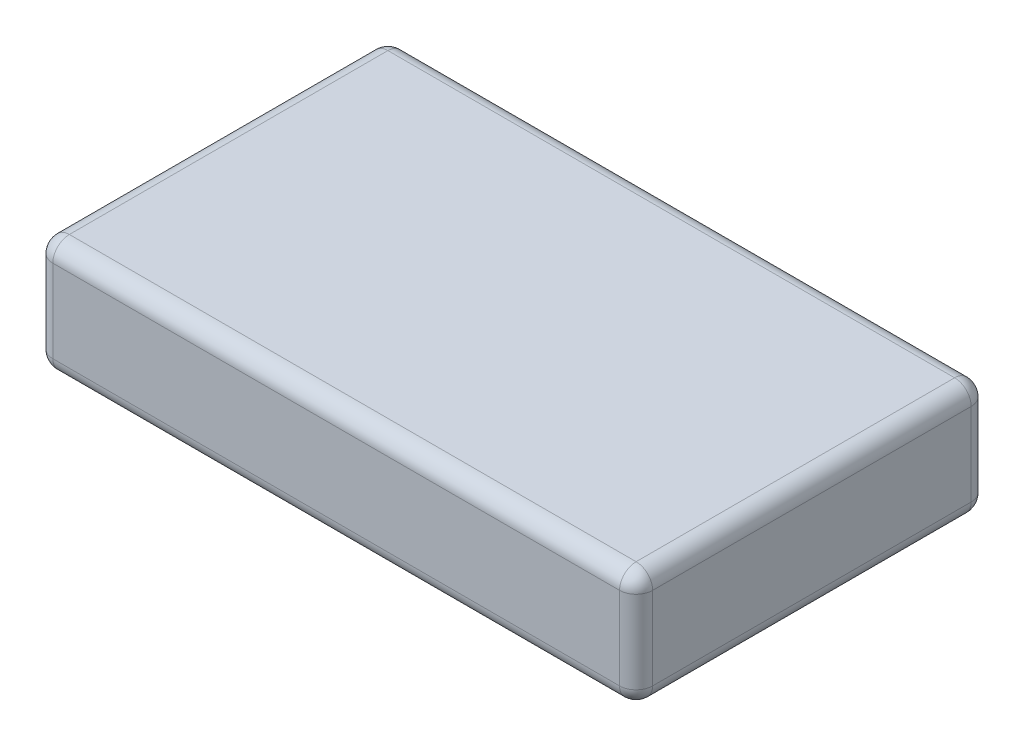
SolidWorks part; units mm, degrees
ref_plane "Front Plane" through (0, 0, 0) normal (0, 0, 1) x (1, 0, 0)
ref_plane "Top Plane" through (0, 0, 0) normal (0, 1, 0) x (1, 0, 0)
ref_plane "Right Plane" through (0, 0, 0) normal (1, 0, 0) x (0, 0, -1)
sketch "Çizim1" plane through (0, 0, 0) normal (0, 1, 0) x (1, 0, 0)
  line L1 (-72.5, -42.5) -> (72.5, -42.5)
  line L2 (-72.5, -42.5) -> (-72.5, 42.5)
  line L3 (-72.5, 42.5) -> (72.5, 42.5)
  line L4 (72.5, -42.5) -> (72.5, 42.5)
  line L5 (-72.5, -42.5) -> (72.5, 42.5) construction
  line L6 (-72.5, 42.5) -> (72.5, -42.5) construction
  point P0 (0, 0)
  dimension "D1" = 145
  dimension "D2" = 85
extrude "Yükseklik-Ekstrüzyon1" add sketch "Çizim1" along normal blind 28
sketch "Çizim2" plane through (-72.5, 0, 0) normal (-1, 0, 0) x (0, 0, 1)
  line L0 (-42.5, 28) -> (42.5, 28) construction
  line L1 (-42.5, 0) -> (42.5, 0) construction
  line L2 (42.5, 28) -> (42.5, 0) construction
  circle A0 centre (22.5, 14) radius 2.75
  circle A1 centre (22.5, 14) radius 0.5
  dimension "D1" = 14
  dimension "D2" = 14
  dimension "D3" = 20
extrude "Kes-Ekstrüzyon1" cut sketch "Çizim2" against normal blind 9
sketch "Çizim3" plane through (-72.5, 0, 0) normal (-1, 0, 0) x (0, 0, 1)
  line L0 (-42.5, 28) -> (42.5, 28) construction
  line L1 (-28.75, 20) -> (-24.25, 20)
  line L2 (-28.75, 20) -> (-28.75, 8)
  line L3 (-28.75, 8) -> (-24.25, 8)
  line L4 (-24.25, 20) -> (-24.25, 8)
  line L5 (-28.75, 20) -> (-24.25, 8) construction
  line L6 (-28.75, 8) -> (-24.25, 20) construction
  line L7 (-42.5, 28) -> (-42.5, 0) construction
  line L9 (-26.6558, 18.9179) -> (-24.6558, 18.9179)
  line L10 (-26.6558, 18.9179) -> (-26.6558, 9.0821)
  line L11 (-26.6558, 9.0821) -> (-24.6558, 9.0821)
  line L12 (-24.6558, 18.9179) -> (-24.6558, 9.0821)
  line L13 (-26.6558, 18.9179) -> (-24.6558, 9.0821) construction
  line L14 (-26.6558, 9.0821) -> (-24.6558, 18.9179) construction
  line L15 (-27.9214, 17.5) -> (-27.0558, 17.5)
  line L16 (-27.9214, 17.5) -> (-27.9214, 10.5)
  line L17 (-27.9214, 10.5) -> (-27.0558, 10.5)
  line L18 (-27.0558, 17.5) -> (-27.0558, 10.5)
  line L19 (-27.9214, 17.5) -> (-27.0558, 10.5) construction
  line L20 (-27.9214, 10.5) -> (-27.0558, 17.5) construction
  point P0 (-26.5, 14)
  point P9 (-25.6558, 14)
  point P14 (-27.4886, 14)
  point P19 (0, 0)
  dimension "D1" = 12
  dimension "D2" = 4.5
  dimension "D3" = 14
  dimension "D4" = 16
  dimension "D5" = 7
  dimension "D6" = 0
  dimension "D7" = 0.4
  dimension "D8" = 2
  dimension "D9" = 0
extrude "Kes-Ekstrüzyon2" cut sketch "Çizim3" against normal blind 9
fillet "Radyus3" radius 4 4 edges at (0, 28, 42.5) (72.5, 28, 0) (0, 28, -42.5) (-72.5, 28, 0)
fillet "Radyus6" radius 4 4 edges at (0, 0, -42.5) (72.5, 0, 0) (0, 0, 42.5) (-72.5, 0, 0)
fillet "Radyus7" radius 4 12 edges at (71.3284, 26.8284, -41.3284) (71.3284, 1.1716, -41.3284) (71.3284, 26.8284, 41.3284) (71.3284, 1.1716, 41.3284) (-71.3284, 26.8284, 41.3284) (-71.3284, 1.1716, 41.3284) (-71.3284, 26.8284, -41.3284) (-71.3284, 1.1716, -41.3284) (72.5, 14, -42.5) (72.5, 14, 42.5) (-72.5, 14, 42.5) (-72.5, 14, -42.5)
